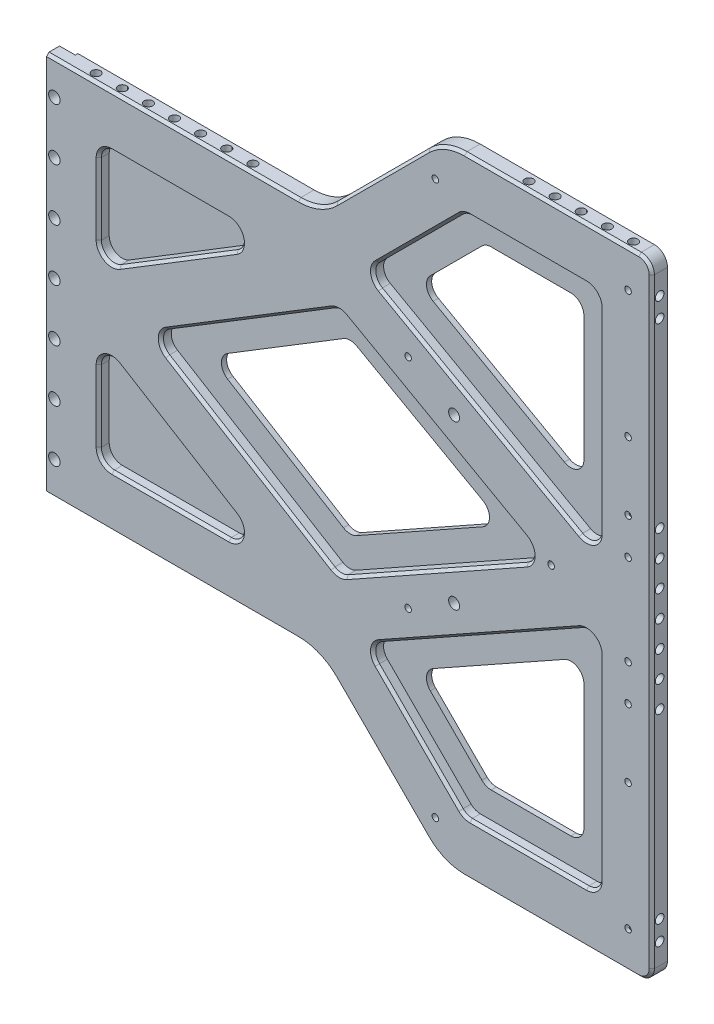
SolidWorks part; units mm, degrees
material "7075-T6 (SN)"
ref_plane "前视基准面" through (0, 0, 0) normal (0, 0, 1) x (1, 0, 0)
ref_plane "上视基准面" through (0, 0, 0) normal (0, 1, 0) x (1, 0, 0)
ref_plane "右视基准面" through (0, 0, 0) normal (1, 0, 0) x (0, 0, -1)
sketch "草图1" plane through (0, 0, 0) normal (0, 0, 1) x (1, 0, 0)
  line L0 (11.5, -73) -> (-13.5, -73) construction
  line L1 (11.5, 73) -> (110.1759, 73)
  line L2 (11.5, 73) -> (11.5, -73)
  line L3 (11.5, -73) -> (110.1759, -73)
  line L5 (387.1759, 0) -> (237.1759, 0) construction
  line L6 (-812.8241, 0) -> (387.1759, 0) construction
  line L7 (237.1759, 120) -> (237.1759, -120)
  line L8 (237.1759, 120) -> (157.1759, 120)
  line L11 (237.1759, -120) -> (157.1759, -120)
  line L12 (157.1759, 120) -> (110.1759, 73)
  line L13 (157.1759, -120) -> (110.1759, -73)
  point P10 (237.1759, 0)
  point P15 (237.1759, 0)
extrude "凸台-拉伸1" add sketch "草图1" against normal blind 1
sketch "草图2" plane through (0, 0, 0) normal (0, 0, 1) x (1, 0, 0)
  line L0 (11.5, 73) -> (5.5, 73)
  line L1 (5.5, 73) -> (5.5, -73)
  line L2 (5.5, -73) -> (11.5, -73)
  line L8 (11.5, 73) -> (11.5, -73)
  line L9 (11.5, -73) -> (110.1759, -73)
  line L10 (110.1759, -73) -> (157.1759, -120)
  line L11 (157.1759, -120) -> (237.1759, -120)
  line L12 (237.1759, -120) -> (237.1759, 120)
  line L13 (237.1759, 120) -> (157.1759, 120)
  line L14 (157.1759, 120) -> (110.1759, 73)
  line L15 (110.1759, 73) -> (11.5, 73)
  line L16 (11.5, 73) -> (11.5, -73) construction
  line L17 (11.5, -73) -> (110.1759, -73)
  line L18 (110.1759, -73) -> (157.1759, -120)
  line L19 (157.1759, -120) -> (237.1759, -120)
  line L20 (237.1759, -120) -> (237.1759, 120)
  line L21 (237.1759, 120) -> (157.1759, 120)
  line L22 (157.1759, 120) -> (110.1759, 73)
  line L23 (110.1759, 73) -> (11.5, 73)
  dimension "D1" = 0
extrude "凸台-拉伸2" add sketch "草图2" along normal blind 5
fillet "圆角1" radius 20 4 edges at (157.1759, 120, 2) (157.1759, -120, 2) (110.1759, -73, 2) (110.1759, 73, 2)
sketch "草图3" plane through (0, 0, 5) normal (0, 0, 1) x (1, 0, 0)
  line L8 (217.1759, 0) -> (117.1989, 56.0448) construction
  line L9 (217.1759, 0) -> (117.1989, -56.0448) construction
  line L11 (25.5, 0) -> (117.1989, 56.0448) construction
  line L12 (25.5, 0) -> (117.1989, -56.0448) construction
  line L13 (237.6263, 0) -> (116.9806, 67.6312)
  line L14 (6.3243, 0) -> (116.9806, 67.6312)
  line L15 (6.3243, 0) -> (116.9806, -67.6312)
  line L16 (217.1759, 100) -> (165.4601, 100)
  line L17 (165.4601, 100) -> (130.1759, 64.7157)
  line L18 (101.8916, 53) -> (25.5, 53)
  line L19 (25.5, 53) -> (25.5, -53)
  line L20 (25.5, -53) -> (101.8916, -53)
  line L21 (130.1759, -64.7157) -> (165.4601, -100)
  line L22 (165.4601, -100) -> (217.1759, -100)
  line L23 (217.1759, -100) -> (217.1759, 100)
  line L24 (217.1759, 100) -> (165.4601, 100)
  line L25 (165.4601, 100) -> (130.1759, 64.7157)
  line L26 (101.8916, 53) -> (25.5, 53)
  line L27 (25.5, 53) -> (25.5, -53)
  line L28 (25.5, -53) -> (101.8916, -53)
  line L29 (130.1759, -64.7157) -> (165.4601, -100)
  line L30 (165.4601, -100) -> (217.1759, -100)
  line L31 (217.1759, -100) -> (217.1759, 100)
  line L32 (237.6263, 0) -> (116.9806, -67.6312)
  line L33 (196.7254, 0) -> (117.4172, 44.4584)
  line L34 (44.6757, 0) -> (117.4172, 44.4584)
  line L35 (44.6757, 0) -> (117.4172, -44.4584)
  line L36 (196.7254, 0) -> (117.4172, -44.4584)
  arc A8 (101.8916, 53) -> (130.1759, 64.7157) centre (101.8916, 93) ccw
  arc A9 (130.1759, -64.7157) -> (101.8916, -53) centre (101.8916, -93) ccw
  arc A10 (101.8916, 53) -> (130.1759, 64.7157) centre (101.8916, 93) ccw
  arc A11 (130.1759, -64.7157) -> (101.8916, -53) centre (101.8916, -93) ccw
  dimension "D2" = 10
  dimension "D1" = 20
  dimension "D3" = 10
extrude "切除-拉伸1" cut sketch "草图3" against normal blind 4 contours L36 L33 L34 L35 | A10 L13 L31 L24 L25 | A11 L29 L30 L31 L32 | L27 L28 L15 | L26 L27 L14 region at (183.7899, 63.6338, 5) region at (183.7899, -63.6338, 5) region at (48.0138, 39.2399, 5) region at (48.0138, -39.2399, 5) region at (119.6061, 0, 5)
fillet "圆角2" radius 5 18 edges at (165.4601, -100, 3) (217.1759, -100, 3) (217.1759, -11.4641, 3) (127.1113, -61.9522, 3) (217.1759, 11.4641, 3) (165.4601, 100, 3) (127.1113, 61.9522, 3) (117.4172, 44.4584, 3) (44.6757, 0, 3) (117.4172, -44.4584, 3) (196.7254, 0, 3) (25.5, -53, 3) (93.0414, -53, 3) (25.5, -11.7198, 3) (25.5, 53, 3) (25.5, 11.7198, 3) (93.0414, 53, 3) (217.1759, 100, 3)
sketch "草图4" plane through (0, 0, 1) normal (0, 0, 1) x (1, 0, 0)
  line L8 (176.275, 0) -> (117.6355, 32.872)
  line L9 (117.6355, 32.872) -> (63.8513, 0)
  line L10 (63.8513, 0) -> (117.6355, -32.872)
  line L11 (117.6355, -32.872) -> (176.275, 0)
  line L12 (176.275, 0) -> (117.6355, 32.872)
  line L13 (117.6355, 32.872) -> (63.8513, 0)
  line L14 (63.8513, 0) -> (117.6355, -32.872)
  line L15 (117.6355, -32.872) -> (176.275, 0)
  line L19 (143.7124, 64.1101) -> (207.1759, 28.5339)
  line L20 (207.1759, 28.5339) -> (207.1759, 90)
  line L21 (207.1759, 90) -> (169.6023, 90)
  line L22 (169.6023, 90) -> (143.7124, 64.1101)
  line L23 (143.7124, 64.1101) -> (207.1759, 28.5339)
  line L24 (207.1759, 28.5339) -> (207.1759, 90)
  line L25 (207.1759, 90) -> (169.6023, 90)
  line L26 (169.6023, 90) -> (143.7124, 64.1101)
  line L31 (143.7124, -64.1101) -> (169.6023, -90)
  line L32 (169.6023, -90) -> (207.1759, -90)
  line L33 (207.1759, -90) -> (207.1759, -28.5339)
  line L34 (207.1759, -28.5339) -> (143.7124, -64.1101)
  line L35 (143.7124, -64.1101) -> (169.6023, -90)
  line L36 (169.6023, -90) -> (207.1759, -90)
  line L37 (207.1759, -90) -> (207.1759, -28.5339)
  line L38 (207.1759, -28.5339) -> (143.7124, -64.1101)
  dimension "D1" = 10
  dimension "D2" = 10
  dimension "D3" = 10
extrude "切除-拉伸2" cut sketch "草图4" against normal blind 5
fillet "圆角3" radius 5 12 edges at (63.8513, 0, 0) (117.6355, 32.872, 0) (176.275, 0, 0) (117.6355, -32.872, 0) (207.1759, 90, 0) (207.1759, 28.5339, 0) (169.6023, 90, 0) (207.1759, -90, 0) (169.6023, -90, 0) (143.7124, -64.1101, 0) (207.1759, -28.5339, 0) (143.7124, 64.1101, 0)
fillet "圆角4" radius 5 2 edges at (237.1759, 120, 2) (237.1759, -120, 2)
chamfer "倒角1" distance 1 angle 45 36 edges at (26.9645, 51.5355, 5) (25.5, 34.3178, 5) (52.8864, 53, 5) (28.0543, 16.2746, 5) (80.0858, 49.3544, 5) (55.4938, 30.0516, 5) (26.9645, -51.5355, 5) (25.5, -34.3178, 5) (52.8864, -53, 5) (28.0543, -16.2746, 5) (80.0858, -49.3544, 5) (55.4938, -30.0516, 5) (49.2635, 0, 5) (83.2874, 23.5989, 5) (83.2874, -23.5989, 5) (117.4322, 43.6643, 5) (117.4322, -43.6643, 5) (154.4582, 23.694, 5) (154.4582, -23.694, 5) (191.5002, 0, 5) (165.6178, -99.6194, 5) (147.9842, -82.5241, 5) (189.8535, -100, 5) (130.5553, -62.2931, 5) (215.7114, -98.5355, 5) (171.3971, -37.1266, 5) (217.1759, -57.4995, 5) (214.7032, -15.6848, 5) (171.3971, 37.1266, 5) (214.7032, 15.6848, 5) (130.5553, 62.2931, 5) (217.1759, 57.4995, 5) (147.9842, 82.5241, 5) (215.7114, 98.5355, 5) (165.6178, 99.6194, 5) (189.8535, 100, 5)
chamfer "倒角2" distance 1 angle 45 13 edges at (53.6958, 73, 5) (109.5453, 74.5224, 5) (133.6759, 96.5, 5) (53.6958, -73, 5) (157.8065, 118.4776, 5) (109.5453, -74.5224, 5) (198.818, 120, 5) (133.6759, -96.5, 5) (235.7114, 118.5355, 5) (157.8065, -118.4776, 5) (237.1759, 0, 5) (198.818, -120, 5) (235.7114, -118.5355, 5)
sketch "草图5" plane through (0, 0, 5) normal (0, 0, 1) x (1, 0, 0)
  circle A0 centre (8.5, 60) radius 2.2
  circle A1 centre (8.5, 40) radius 2.2
  circle A2 centre (8.5, 20) radius 2.2
  circle A3 centre (8.5, 0) radius 2.2
  circle A4 centre (8.5, -20) radius 2.2
  circle A5 centre (8.5, -40) radius 2.2
  circle A6 centre (8.5, -60) radius 2.2
  point P0 (8.5, 60)
  point P1 (8.5, 40)
  point P3 (8.5, 20)
  point P5 (8.5, 0)
  point P7 (8.5, -20)
  point P9 (8.5, -40)
  point P11 (8.5, -60)
  dimension "D1" = 7
extrude "切除-拉伸3" cut sketch "草图5" against normal through all both and the other way through all
hole_wizard "M4 螺纹孔1" positions "草图7" profile "草图8" tap size "M4" standard "GB"
sketch "草图7" plane through (0, -73, 0) normal (0, -1, 0) x (-1, 0, 0)
  point P0 (-81.5, -2)
  point P3 (-71.5, -2)
  point P6 (-61.5, -2)
  point P9 (-51.5, -2)
  point P12 (-41.5, -2)
  point P15 (-31.5, -2)
  point P18 (-21.5, -2)
sketch "草图8" plane through (81.5, -73, 2) normal (1, 0, 0) x (0, 0, -1)
  line L0 (0, 0) -> (0, 11.0914)
  line L1 (0, 11.0914) -> (1.65, 10.1)
  line L2 (1.65, 10.1) -> (1.65, 0)
  line L5 (1.65, 0) -> (0, 0)
  line L10 (0, 11.0914) -> (-1.65, 10.1) construction
  line L11 (0, -6.35) -> (0, 107.95) construction
  dimension "螺纹孔钻头直径" = 3.3
  dimension "螺纹孔钻头深度" = 10.1
  dimension "导头角度" = 118
cosmetic thread "孔螺蚊线1" parameters "D1"=8, "D2"=4
cosmetic thread "孔螺蚊线2" parameters "D1"=8, "D2"=4
cosmetic thread "孔螺蚊线3" parameters "D1"=8, "D2"=4
cosmetic thread "孔螺蚊线4" parameters "D1"=8, "D2"=4
cosmetic thread "孔螺蚊线5" parameters "D1"=8, "D2"=4
cosmetic thread "孔螺蚊线6" parameters "D1"=8, "D2"=4
cosmetic thread "孔螺蚊线7" parameters "D1"=8, "D2"=4
mirror "镜向1" about plane through (0, 0, 0) normal (0, 1, 0) of "M4 螺纹孔1"
cosmetic thread "孔螺蚊线8" parameters "D1"=8, "D2"=4
cosmetic thread "孔螺蚊线9" parameters "D1"=8, "D2"=4
cosmetic thread "孔螺蚊线10" parameters "D1"=8, "D2"=4
cosmetic thread "孔螺蚊线11" parameters "D1"=8, "D2"=4
cosmetic thread "孔螺蚊线12" parameters "D1"=8, "D2"=4
cosmetic thread "孔螺蚊线13" parameters "D1"=8, "D2"=4
cosmetic thread "孔螺蚊线14" parameters "D1"=8, "D2"=4
hole_wizard "M4 螺纹孔2" positions "草图10" profile "草图11" tap size "M4" standard "GB"
sketch "草图10" plane through (0, -120, 0) normal (0, -1, 0) x (-1, 0, 0)
  point P0 (-227.1759, -2)
  point P3 (-217.1759, -2)
  point P6 (-207.1759, -2)
  point P9 (-197.1759, -2)
  point P12 (-187.1759, -2)
sketch "草图11" plane through (227.1759, -120, 2) normal (1, 0, 0) x (0, 0, -1)
  line L0 (0, 0) -> (0, 11.0914)
  line L1 (0, 11.0914) -> (1.65, 10.1)
  line L2 (1.65, 10.1) -> (1.65, 0)
  line L5 (1.65, 0) -> (0, 0)
  line L10 (0, 11.0914) -> (-1.65, 10.1) construction
  line L11 (0, -6.35) -> (0, 107.95) construction
  dimension "螺纹孔钻头直径" = 3.3
  dimension "螺纹孔钻头深度" = 10.1
  dimension "导头角度" = 118
cosmetic thread "孔螺蚊线15" parameters "D1"=8, "D2"=4
cosmetic thread "孔螺蚊线16" parameters "D1"=8, "D2"=4
cosmetic thread "孔螺蚊线17" parameters "D1"=8, "D2"=4
cosmetic thread "孔螺蚊线18" parameters "D1"=8, "D2"=4
cosmetic thread "孔螺蚊线19" parameters "D1"=8, "D2"=4
mirror "镜向2" about plane through (0, 0, 0) normal (0, 1, 0) of "M4 螺纹孔2"
cosmetic thread "孔螺蚊线20" parameters "D1"=8, "D2"=4
cosmetic thread "孔螺蚊线21" parameters "D1"=8, "D2"=4
cosmetic thread "孔螺蚊线22" parameters "D1"=8, "D2"=4
cosmetic thread "孔螺蚊线23" parameters "D1"=8, "D2"=4
cosmetic thread "孔螺蚊线24" parameters "D1"=8, "D2"=4
hole_wizard "M4 螺纹孔3" positions "草图13" profile "草图14" tap size "M4" standard "GB"
sketch "草图13" plane through (237.1759, 0, 0) normal (1, 0, 0) x (0, 0, -1)
  point P0 (-2, -99.5)
  point P3 (-2, -107)
sketch "草图14" plane through (237.1759, -99.5, 2) normal (0, 1, 0) x (0, 0, -1)
  line L0 (0, 0) -> (0, 11.0914)
  line L1 (0, 11.0914) -> (1.65, 10.1)
  line L2 (1.65, 10.1) -> (1.65, 0)
  line L5 (1.65, 0) -> (0, 0)
  line L10 (0, 11.0914) -> (-1.65, 10.1) construction
  line L11 (0, -6.35) -> (0, 107.95) construction
  dimension "螺纹孔钻头直径" = 3.3
  dimension "螺纹孔钻头深度" = 10.1
  dimension "导头角度" = 118
cosmetic thread "孔螺蚊线26" parameters "D1"=8, "D2"=4
cosmetic thread "孔螺蚊线27" parameters "D1"=8, "D2"=4
mirror "镜向3" about plane through (0, 0, 0) normal (0, 1, 0) of "M4 螺纹孔3"
cosmetic thread "孔螺蚊线28" parameters "D1"=8, "D2"=4
cosmetic thread "孔螺蚊线29" parameters "D1"=8, "D2"=4
sketch "草图15" plane through (0, 0, 5) normal (0, 0, 1) x (1, 0, 0)
  line L0 (151.5, 0) -> (161.5, 0) construction
  line L1 (151.5, 70) -> (151.5, -70) construction
  line L2 (-812.8241, 0) -> (387.1759, 0) construction
  line L3 (133.4954, -36.5917) -> (142.2972, -52.293) construction
  line L4 (189.4341, -5.2337) -> (120.4603, -43.8989) construction
  line L5 (132.5744, -57.7433) -> (209.2419, -14.7652) construction
  line L6 (89.7964, -71.4061) -> (185.9962, -17.4786) construction
  line L7 (161.5, 31.2106) -> (161.5, -31.2106) construction
  point P15 (137.8963, -44.4423)
  point P18 (161.5, 0)
hole_wizard "M5 螺纹孔1" positions "草图16" profile "草图17" tap size "M5" standard "GB"
sketch "草图16" plane through (0, 0, 5) normal (0, 0, 1) x (1, 0, 0)
  point P0 (161.5, 31.2106)
  point P3 (161.5, -31.2106)
sketch "草图17" plane through (161.5, 31.2106, 5) normal (1, 0, 0) x (0, -1, 0)
  line L0 (0, 0) -> (0, 13.6618)
  line L1 (0, 13.6618) -> (2.1, 12.4)
  line L2 (2.1, 12.4) -> (2.1, 0)
  line L5 (2.1, 0) -> (0, 0)
  line L10 (0, 13.6618) -> (-2.1, 12.4) construction
  line L11 (0, -6.35) -> (0, 107.95) construction
  dimension "螺纹孔钻头直径" = 4.2
  dimension "螺纹孔钻头深度" = 12.4
  dimension "导头角度" = 118
cosmetic thread "孔螺蚊线30" parameters "D1"=10, "D2"=5
cosmetic thread "孔螺蚊线31" parameters "D1"=10, "D2"=5
sketch "草图18" plane through (237.1759, 0, 0) normal (1, 0, 0) x (0, 0, -1)
  line L0 (1, 0) -> (-5, 0) construction
  line L1 (1, -115) -> (1, 115) construction
  line L2 (-2, 10) -> (-2, -10) construction
  line L3 (-2, 20) -> (-2, -20) construction
  line L4 (-2, 30) -> (-2, -30) construction
  point P8 (-2, 0)
  point P12 (-2, 0)
  point P15 (-2, 0)
hole_wizard "M4 螺纹孔4" positions "草图19" profile "草图20" tap size "M4" standard "GB"
sketch "草图19" plane through (237.1759, 0, 0) normal (1, 0, 0) x (0, 0, -1)
  line L0 (-2, 10) -> (-2, -10) construction
  point P0 (-2, 30)
  point P3 (-2, 20)
  point P6 (-2, 10)
  point P9 (-2, 0)
  point P13 (-2, -10)
  point P16 (-2, -20)
  point P19 (-2, -30)
sketch "草图20" plane through (237.1759, 30, 2) normal (0, 1, 0) x (0, 0, -1)
  line L0 (0, 0) -> (0, 11.0914)
  line L1 (0, 11.0914) -> (1.65, 10.1)
  line L2 (1.65, 10.1) -> (1.65, 0)
  line L5 (1.65, 0) -> (0, 0)
  line L10 (0, 11.0914) -> (-1.65, 10.1) construction
  line L11 (0, -6.35) -> (0, 107.95) construction
  dimension "螺纹孔钻头直径" = 3.3
  dimension "螺纹孔钻头深度" = 10.1
  dimension "导头角度" = 118
cosmetic thread "孔螺蚊线32" parameters "D1"=8, "D2"=4
cosmetic thread "孔螺蚊线33" parameters "D1"=8, "D2"=4
cosmetic thread "孔螺蚊线34" parameters "D1"=8, "D2"=4
cosmetic thread "孔螺蚊线35" parameters "D1"=8, "D2"=4
cosmetic thread "孔螺蚊线36" parameters "D1"=8, "D2"=4
cosmetic thread "孔螺蚊线37" parameters "D1"=8, "D2"=4
cosmetic thread "孔螺蚊线38" parameters "D1"=8, "D2"=4
sketch "草图21" plane through (0, 0, 5) normal (0, 0, 1) x (1, 0, 0)
  line L0 (161.5, -31.2106) -> (143.9, -31.2106)
  line L1 (143.9, -31.2106) -> (143.9, -41.7006)
  line L3 (161.5, -31.2106) -> (161.5, -105.8306)
  line L4 (161.5, -105.8306) -> (154.33, -105.8306)
  line L5 (161.5, -31.2106) -> (198.64, -31.2106)
  line L6 (198.64, -31.2106) -> (198.64, -0.0706)
  line L7 (228.08, -31.2106) -> (228.08, -17.3206)
  line L8 (198.64, -31.2106) -> (228.08, -31.2106)
  line L9 (228.08, -31.2106) -> (228.08, -57.3206)
  line L10 (228.08, -57.3206) -> (228.08, -105.8406)
hole_wizard "M3 螺纹孔1" positions "草图22" profile "草图23" tap size "M3" standard "GB"
sketch "草图22" plane through (0, 0, 5) normal (0, 0, 1) x (1, 0, 0)
  point P0 (143.9, -41.7006)
  point P3 (154.33, -105.8306)
  point P6 (198.64, 0.0706)
  point P8 (228.08, -31.2106)
  point P11 (228.08, -17.3206)
  point P14 (228.08, -105.8406)
  point P17 (228.08, -57.3206)
sketch "草图23" plane through (143.9, -41.7006, 5) normal (1, 0, 0) x (0, -1, 0)
  line L0 (0, 0) -> (0, 8.2511)
  line L1 (0, 8.2511) -> (1.25, 7.5)
  line L2 (1.25, 7.5) -> (1.25, 0)
  line L5 (1.25, 0) -> (0, 0)
  line L10 (0, 8.2511) -> (-1.25, 7.5) construction
  line L11 (0, -6.35) -> (0, 107.95) construction
  dimension "螺纹孔钻头直径" = 2.5
  dimension "螺纹孔钻头深度" = 7.5
  dimension "导头角度" = 118
cosmetic thread "孔螺蚊线39" parameters "D1"=6, "D2"=3
cosmetic thread "孔螺蚊线40" parameters "D1"=6, "D2"=3
cosmetic thread "孔螺蚊线41" parameters "D1"=6, "D2"=3
cosmetic thread "孔螺蚊线42" parameters "D1"=6, "D2"=3
cosmetic thread "孔螺蚊线43" parameters "D1"=6, "D2"=3
cosmetic thread "孔螺蚊线44" parameters "D1"=6, "D2"=3
cosmetic thread "孔螺蚊线45" parameters "D1"=6, "D2"=3
mirror "镜向4" about plane through (0, 0, 0) normal (0, 1, 0) of "M3 螺纹孔1"
cosmetic thread "孔螺蚊线46" parameters "D1"=6, "D2"=3
cosmetic thread "孔螺蚊线47" parameters "D1"=6, "D2"=3
cosmetic thread "孔螺蚊线48" parameters "D1"=6, "D2"=3
cosmetic thread "孔螺蚊线49" parameters "D1"=6, "D2"=3
cosmetic thread "孔螺蚊线50" parameters "D1"=6, "D2"=3
cosmetic thread "孔螺蚊线51" parameters "D1"=6, "D2"=3
cosmetic thread "孔螺蚊线52" parameters "D1"=6, "D2"=3
